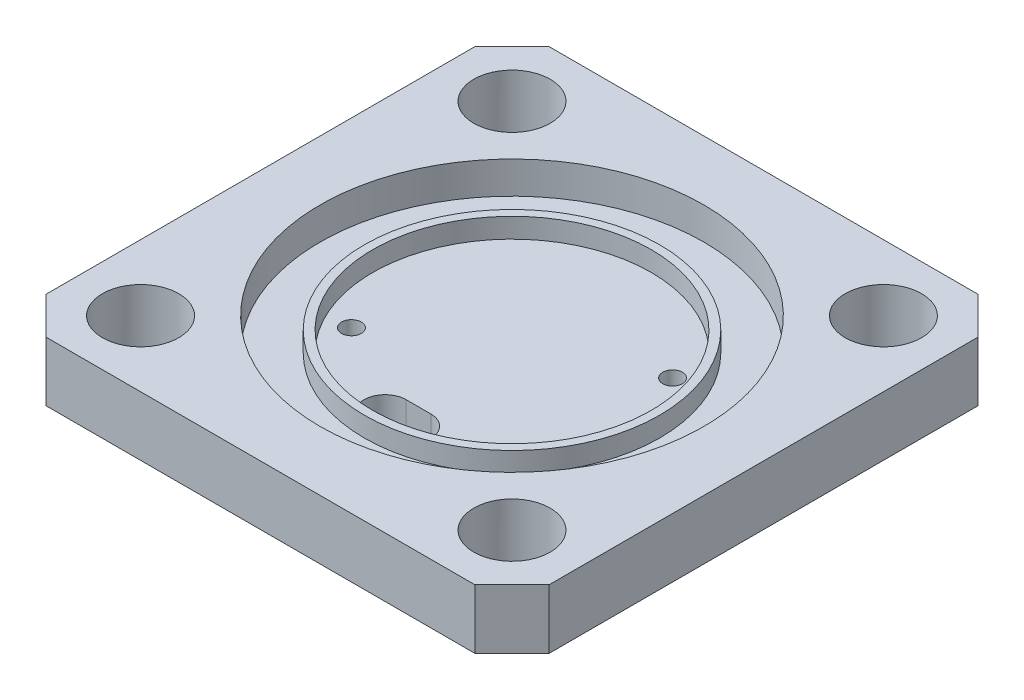
SolidWorks part; units mm, degrees
ref_plane "Front Plane" through (0, 0, 0) normal (0, 0, 1) x (1, 0, 0)
ref_plane "Top Plane" through (0, 0, 0) normal (0, 1, 0) x (1, 0, 0)
ref_plane "Right Plane" through (0, 0, 0) normal (1, 0, 0) x (0, 0, -1)
sketch "Sketch1" plane through (0, 0, 0) normal (0, 1, 0) x (1, 0, 0)
  line L1 (-20.32, -20.32) -> (20.32, -20.32)
  line L2 (-20.32, -20.32) -> (-20.32, 20.32)
  line L3 (-20.32, 20.32) -> (20.32, 20.32)
  line L4 (20.32, -20.32) -> (20.32, 20.32)
  line L5 (-20.32, -20.32) -> (20.32, 20.32) construction
  line L6 (-20.32, 20.32) -> (20.32, -20.32) construction
  point P0 (0, 0)
  dimension "D1" = 40.64
  dimension "D2" = 40.64
extrude "Boss-Extrude1" add sketch "Sketch1" along normal blind 4.8
sketch "Sketch2" plane through (0, 4.8, 0) normal (0, 1, 0) x (1, 0, 0)
  line L1 (-15, -15) -> (15, -15) construction
  line L2 (-15, -15) -> (-15, 15) construction
  line L3 (-15, 15) -> (15, 15) construction
  line L4 (15, -15) -> (15, 15) construction
  line L5 (-15, -15) -> (15, 15) construction
  line L6 (-15, 15) -> (15, -15) construction
  circle A0 centre (-15, 15) radius 3.085
  circle A1 centre (15, 15) radius 3.085
  circle A2 centre (15, -15) radius 3.085
  circle A3 centre (-15, -15) radius 3.085
  point P0 (0, 0)
  dimension "D3" = 6.17
  dimension "D1" = 30
  dimension "D2" = 30
  dimension "D4" = 2
  dimension "D5" = 2
extrude "Cut-Extrude1" cut sketch "Sketch2" against normal up to next contours A0 | A1 | A2 | A3
chamfer "Chamfer1" distance 3 angle 45 4 edges at (-20.32, 2.4, 20.32) (20.32, 2.4, 20.32) (20.32, 2.4, -20.32) (-20.32, 2.4, -20.32)
sketch "Sketch3" plane through (0, 4.8, 0) normal (0, 1, 0) x (1, 0, 0)
  circle A0 centre (0, 0) radius 11.25
  dimension "D1" = 22.5
extrude "Cut-Extrude2" cut sketch "Sketch3" against normal blind 2.6
ref_point "Point1"
sketch "Sketch4" plane through (0, 4.8, 0) normal (0, 1, 0) x (1, 0, 0)
  circle A0 centre (0, 0) radius 12000
  circle A1 centre (0, 0) radius 15.5
  circle A2 centre (0, 0) radius 11.925
  dimension "D1" = 24000
  dimension "D2" = 31
  dimension "D3" = 23.85
extrude "Cut-Extrude3" cut sketch "Sketch4" against normal blind 2.6 contours A1 A2 region at (-15.0616, 4.8, 0)
sketch "Sketch5" plane through (0, 2.2, 0) normal (0, 1, 0) x (1, 0, 0)
  line L0 (0, 0) -> (0, -11.25) construction
  line L1 (-1, -9.25) -> (1, -9.25) construction
  line L2 (-1, -11.25) -> (1, -11.25) construction
  line L3 (-1, -11.25) -> (-1, -7.25) construction
  line L4 (-1, -7.25) -> (1, -7.25) construction
  line L5 (1, -11.25) -> (1, -7.25) construction
  line L6 (-1, -11.25) -> (1, -7.25) construction
  line L7 (-1, -7.25) -> (1, -11.25) construction
  line L8 (-1, -7.55) -> (1, -7.55)
  line L9 (-1, -10.95) -> (1, -10.95)
  circle A0 centre (0, 0) radius 11.25 construction
  circle A1 centre (0, 0) radius 9.25 construction
  arc A2 (-1, -7.55) -> (-1, -10.95) centre (-1, -9.25) ccw
  arc A7 (1, -10.95) -> (1, -7.55) centre (1, -9.25) ccw
  point P6 (0, -9.25)
  point P14 (0, -9.25)
  dimension "D1" = 4
  dimension "D2" = 2
  dimension "D3" = 0
  dimension "D4" = 3.4
extrude "Cut-Extrude4" cut sketch "Sketch5" against normal through all contours L9 A7 L8 A2
sketch "Sketch6" plane through (0, 4.8, 0) normal (0, 1, 0) x (1, 0, 0)
  circle A3 centre (0, 0) radius 11.25 construction
  circle A4 centre (0, 0) radius 11.25
  circle A5 centre (0, 0) radius 11.925
  circle A8 centre (0, 0) radius 11.925
  dimension "D1" = 0
extrude "Cut-Extrude5" cut sketch "Sketch6" against normal blind 1
sketch "Sketch7" plane through (0, 2.2, 0) normal (0, 1, 0) x (1, 0, 0)
  line L0 (8.2431, 4.7273) -> (-8.2431, -4.7273) construction
  circle A0 centre (8.2431, 4.7273) radius 0.8
  circle A1 centre (0, 0) radius 11.25
  circle A2 centre (0, 0) radius 11.25 construction
  circle A3 centre (8.2431, 4.7273) radius 1
  circle A4 centre (8.2431, 4.7273) radius 1 construction
  circle A5 centre (-8.2431, -4.7273) radius 1
  circle A6 centre (-8.2431, -4.7273) radius 1 construction
  circle A7 centre (0, 0) radius 11
  circle A8 centre (0, 0) radius 11 construction
  circle A9 centre (-8.2431, -4.7273) radius 0.8
  dimension "D5" = 1.6
  dimension "D6" = 1.6
  dimension "D1" = 0
  dimension "D2" = 0
  dimension "D3" = 0
  dimension "D4" = 0
extrude "Cut-Extrude6" cut sketch "Sketch7" against normal through all contours A9 | A0 | A0 region at (8.2431, 2.2, -4.7273) region at (-8.2431, 2.2, 4.7273)
